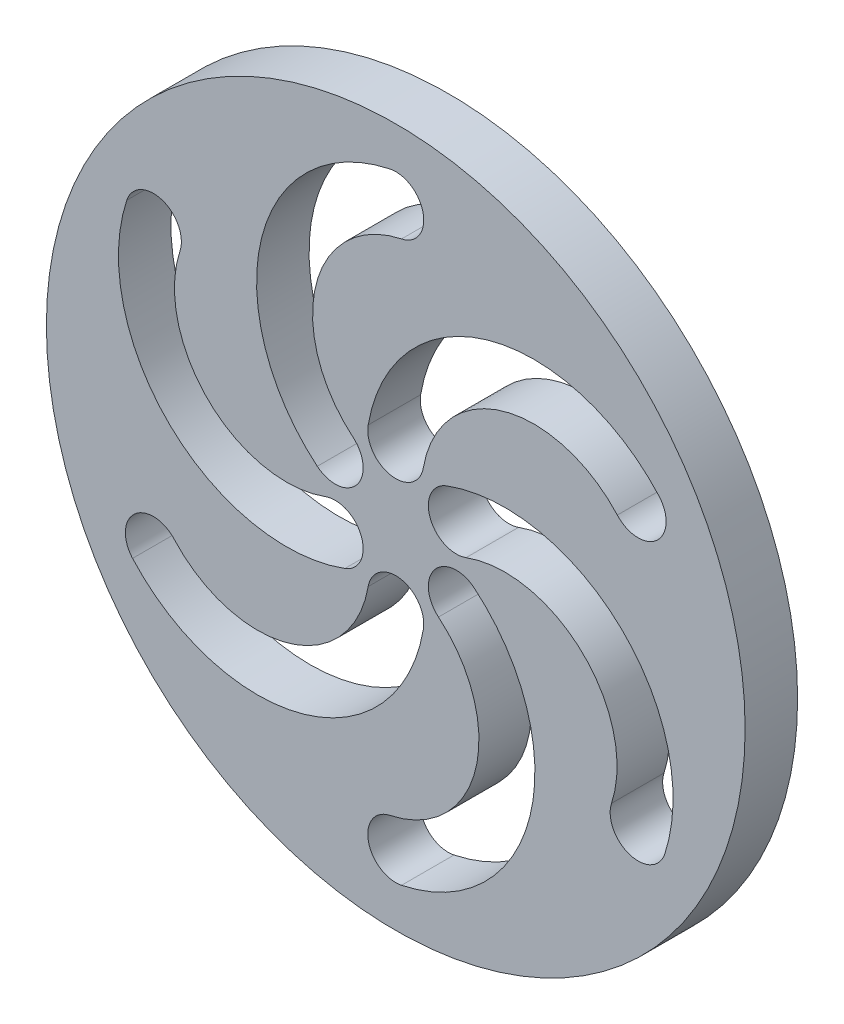
SolidWorks part; units mm, degrees
ref_plane "Front Plane" through (0, 0, 0) normal (0, 0, 1) x (1, 0, 0)
ref_plane "Top Plane" through (0, 0, 0) normal (0, 1, 0) x (1, 0, 0)
ref_plane "Right Plane" through (0, 0, 0) normal (1, 0, 0) x (0, 0, -1)
sketch "Sketch1" plane through (0, 0, 0) normal (0, 0, 1) x (1, 0, 0)
  line L0 (0, 60.505) -> (0, -60.505) construction
  line L1 (-16.0502, -9.2666) -> (16.0502, 9.2666) construction
  line L2 (0, 0) -> (0, 6.35) construction
  line L3 (0, 0) -> (5.4993, 3.175) construction
  circle A0 centre (0, 0) radius 31.7062
  arc A1 (2.5035, 5.9211) -> (-2.5035, 6.7789) centre (0, 6.35) cw
  arc A2 (-2.5035, 6.7789) -> (23.8868, 14.3971) centre (12.535, 4.2025) cw
  arc A3 (23.8868, 14.3971) -> (20.1073, 11.0029) centre (21.997, 12.7) cw
  arc A4 (20.1073, 11.0029) -> (2.5035, 5.9211) centre (12.535, 4.2025) ccw
  arc A5 (4.6189, 5.5576) -> (24.4117, -13.488) centre (9.907, -8.7544) cw
  arc A6 (6.3796, 0.7924) -> (4.6189, 5.5576) centre (5.4993, 3.175) cw
  arc A7 (19.5824, -11.912) -> (6.3796, 0.7924) centre (9.907, -8.7544) ccw
  arc A8 (24.4117, -13.488) -> (19.5824, -11.912) centre (21.997, -12.7) cw
  arc A9 (7.1225, -1.2213) -> (0.5249, -27.8852) centre (-2.628, -12.9569) cw
  arc A10 (3.8761, -5.1287) -> (7.1225, -1.2213) centre (5.4993, -3.175) cw
  arc A11 (-0.5249, -22.9148) -> (3.8761, -5.1287) centre (-2.628, -12.9569) ccw
  arc A12 (0.5249, -27.8852) -> (-0.5249, -22.9148) centre (0, -25.4) cw
  arc A13 (2.5035, -6.7789) -> (-23.8868, -14.3971) centre (-12.535, -4.2025) cw
  arc A14 (-2.5035, -5.9211) -> (2.5035, -6.7789) centre (0, -6.35) cw
  arc A15 (-20.1073, -11.0029) -> (-2.5035, -5.9211) centre (-12.535, -4.2025) ccw
  arc A16 (-23.8868, -14.3971) -> (-20.1073, -11.0029) centre (-21.997, -12.7) cw
  arc A17 (-4.6189, -5.5576) -> (-24.4117, 13.488) centre (-9.907, 8.7544) cw
  arc A18 (-6.3796, -0.7924) -> (-4.6189, -5.5576) centre (-5.4993, -3.175) cw
  arc A19 (-19.5824, 11.912) -> (-6.3796, -0.7924) centre (-9.907, 8.7544) ccw
  arc A20 (-24.4117, 13.488) -> (-19.5824, 11.912) centre (-21.997, 12.7) cw
  arc A21 (-7.1225, 1.2213) -> (-0.5249, 27.8852) centre (2.628, 12.9569) cw
  arc A22 (-3.8761, 5.1287) -> (-7.1225, 1.2213) centre (-5.4993, 3.175) cw
  arc A23 (0.5249, 22.9148) -> (-3.8761, 5.1287) centre (2.628, 12.9569) ccw
  arc A24 (-0.5249, 27.8852) -> (0.5249, 22.9148) centre (0, 25.4) cw
  point P6 (0, 0)
  point P17 (0, 0)
  dimension "D2" = 2.54
  dimension "D1" = 6.35
  dimension "D3" = 60
  dimension "D4" = 25.4
  dimension "D6" = 60
  dimension "D5" = 6
extrude "Boss-Extrude1" add sketch "Sketch1" along normal blind 4.7625
equation "\"slot-width\"=0.1"
equation "\"D2@Sketch1\"= \"slot-width\""
equation "\"slot-end-angle\"=60"
equation "\"D3@Sketch1\"=\"slot-end-angle\""
equation "\"slot-spacing-angle\"=60"
equation "\"D6@Sketch1\"=\"slot-spacing-angle\""
equation "\"slot-gap\"=0.01"
equation "\"pulley-thickness\"=0.25"
equation "\"pin-diameter\"=2*\"slot-width\"-2*\"slot-gap\""
